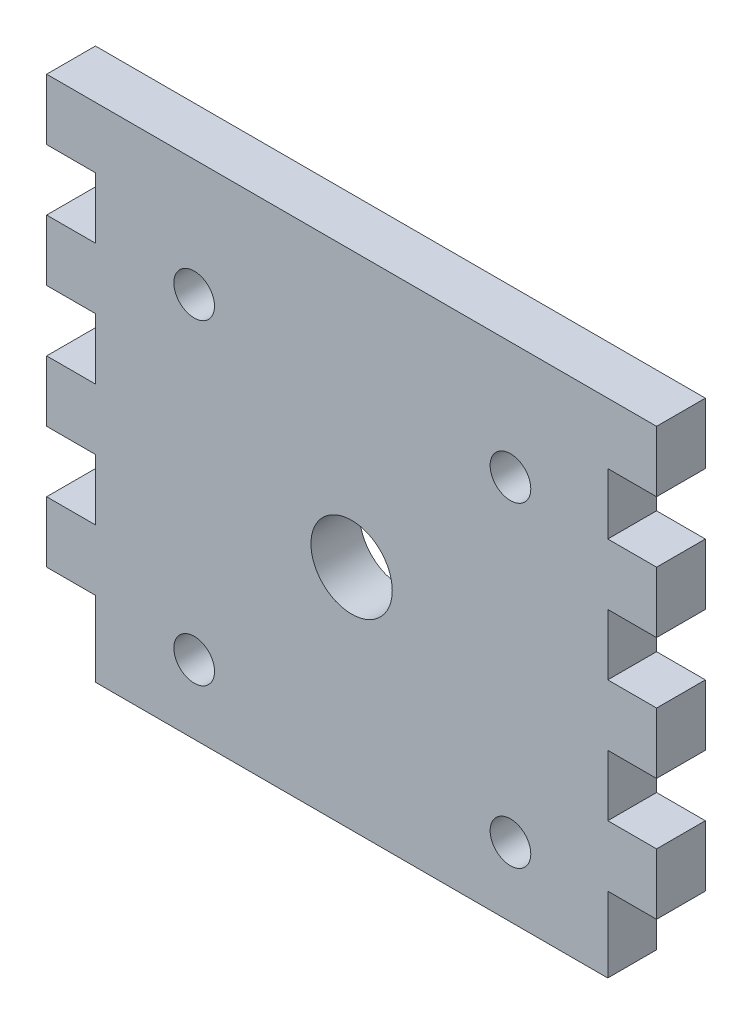
SolidWorks part; units mm, degrees
material "Thornel VCB-20 Carbon Cloth"
ref_plane "Front Plane" through (0, 0, 0) normal (0, 0, 1) x (1, 0, 0)
ref_plane "Top Plane" through (0, 0, 0) normal (0, 1, 0) x (1, 0, 0)
ref_plane "Right Plane" through (0, 0, 0) normal (1, 0, 0) x (0, 0, -1)
sketch "Sketch1" plane through (0, 0, 0) normal (0, 0, 1) x (1, 0, 0)
  line L1 (-37.8801, 17.0433) -> (38.3199, 17.0433)
  line L2 (-37.8801, 17.0433) -> (-37.8801, -59.1567)
  line L3 (-37.8801, -59.1567) -> (38.3199, -59.1567)
  line L4 (38.3199, 17.0433) -> (38.3199, -59.1567)
  dimension "D1" = 76.2
  dimension "D2" = 76.2
extrude "Boss-Extrude1" add sketch "Sketch1" along normal blind 6.35
sketch "Sketch2" plane through (0, 0, 6.35) normal (0, 0, 1) x (1, 0, 0)
  line L0 (-37.8801, 17.0433) -> (-31.5301, 17.0433)
  line L1 (38.3199, 17.0433) -> (-37.8801, 17.0433) construction
  line L2 (-31.5301, 17.0433) -> (-31.5301, 9.4233)
  line L3 (-31.5301, 9.4233) -> (-37.8801, 9.4233)
  line L4 (-37.8801, 17.0433) -> (-37.8801, -59.1567) construction
  line L5 (-37.8801, 9.4233) -> (-37.8801, 1.8033)
  line L6 (-37.8801, 1.8033) -> (-31.5301, 1.8033)
  line L7 (-31.5301, 1.8033) -> (-31.5301, -5.8167)
  line L8 (-31.5301, -5.8167) -> (-37.8801, -5.8167)
  line L9 (-37.8801, -5.8167) -> (-37.8801, -13.4367)
  line L10 (-37.8801, -13.4367) -> (-31.5301, -13.4367)
  line L11 (-31.5301, -13.4367) -> (-31.5301, -21.0567)
  line L12 (-31.5301, -21.0567) -> (-37.8801, -21.0567)
  line L13 (-37.8801, -21.0567) -> (-46.7258, -21.0567)
  line L14 (-37.8801, -21.0567) -> (-37.8801, -28.6767) [skipped]
  line L15 (-46.7258, -21.0567) -> (-46.7258, 17.0433)
  line L16 (-46.7258, 17.0433) -> (-37.8801, 17.0433)
  line L19 (47.1657, -21.0567) -> (47.1657, 17.0433)
  line L20 (38.3199, -21.0567) -> (47.1657, -21.0567)
  line L21 (31.9699, -21.0567) -> (38.3199, -21.0567)
  line L22 (31.9699, -13.4367) -> (31.9699, -21.0567)
  line L23 (38.3199, -13.4367) -> (31.9699, -13.4367)
  line L24 (38.3199, -5.8167) -> (38.3199, -13.4367)
  line L25 (31.9699, -5.8167) -> (38.3199, -5.8167)
  line L26 (31.9699, 1.8033) -> (31.9699, -5.8167)
  line L27 (38.3199, 1.8033) -> (31.9699, 1.8033)
  line L28 (38.3199, 9.4233) -> (38.3199, 1.8033)
  line L29 (31.9699, 9.4233) -> (38.3199, 9.4233)
  line L30 (31.9699, 17.0433) -> (31.9699, 9.4233)
  line L31 (38.3199, 17.0433) -> (31.9699, 17.0433)
  line L32 (47.1657, 17.0433) -> (38.3199, 17.0433)
  dimension "D1" = 7.62
  dimension "D2" = 7.62
  dimension "D3" = 6.35
  dimension "D4" = 6.35
  dimension "D6" = 38.1
  dimension "D5" = 3
extrude "Cut-Extrude1" cut sketch "Sketch2" against normal blind 6.35
sketch "Sketch3" plane through (0, 0, 6.35) normal (0, 0, 1) x (1, 0, 0)
  line L1 (-31.5301, -21.0567) -> (-37.8801, -21.0567)
  line L2 (-31.5301, -21.0567) -> (-31.5301, -59.1567)
  line L3 (-31.5301, -59.1567) -> (-37.8801, -59.1567)
  line L4 (-37.8801, -21.0567) -> (-37.8801, -59.1567)
  line L5 (31.9699, -21.0567) -> (38.3199, -21.0567)
  line L6 (31.9699, -21.0567) -> (31.9699, -59.1567)
  line L7 (31.9699, -59.1567) -> (38.3199, -59.1567)
  line L8 (38.3199, -21.0567) -> (38.3199, -59.1567)
extrude "Cut-Extrude2" cut sketch "Sketch3" against normal blind 6.35
sketch "Sketch4" plane through (0, 0, 6.35) normal (0, 0, 1) x (1, 0, 0)
  line L0 (-31.5301, -13.4367) -> (-31.5301, -21.0567)
  line L1 (-31.5301, -59.1567) -> (-31.5301, -13.4367) construction
  line L2 (-31.5301, -21.0567) -> (-37.6261, -21.0567)
  line L3 (-37.6261, -21.0567) -> (-37.6261, -28.6767)
  line L4 (-37.6261, -28.6767) -> (-31.5301, -28.6767)
  line L5 (-31.5301, -21.0567) -> (-31.5301, -28.6767)
  line L6 (0.2199, 17.0433) -> (0.2199, -59.1567)
  line L7 (31.9699, 17.0433) -> (-31.5301, 17.0433) construction
  line L8 (-31.5301, -59.1567) -> (31.9699, -59.1567) construction
  line L9 (31.9699, -21.0567) -> (38.0659, -21.0567)
  line L10 (38.0659, -21.0567) -> (38.0659, -28.6767)
  line L11 (38.0659, -28.6767) -> (31.9699, -28.6767)
  line L12 (31.9699, -21.0567) -> (31.9699, -28.6767)
  line M6 (-31.5301, -13.4367) -> (-31.5301, -59.1567)
  line M8 (31.9699, -59.1567) -> (31.9699, -13.4367)
  dimension "D1" = 7.62
  dimension "D2" = 7.62
  dimension "D3" = 6.096
  dimension "D4" = 6.096
extrude "Boss-Extrude3" add sketch "Sketch4" against normal blind 6.096 contours L3 L4 L2 M6 | L11 L10 L9 M8 region at (-34.5781, -24.8667, 6.35) region at (35.0179, -24.8667, 6.35)
sketch "Sketch5" plane through (0, 17.0433, 0) normal (0, 1, 0) x (1, 0, 0)
  line L1 (-31.5301, 0) -> (31.9699, 0)
  line L2 (-31.5301, 0) -> (-31.5301, -6.35)
  line L3 (-31.5301, -6.35) -> (31.9699, -6.35)
  line L4 (31.9699, 0) -> (31.9699, -6.35)
extrude "Cut-Extrude3" cut sketch "Sketch5" against normal blind 7.62
sketch "Sketch6" plane through (0, 0, 6.35) normal (0, 0, 1) x (1, 0, 0)
  line L0 (-31.5301, -59.1567) -> (31.9699, -59.1567) construction
  line L1 (-19.4468, -5.1999) -> (0.2199, -24.8667) construction
  line L2 (0.2199, -24.8667) -> (-37.8801, -24.8667) construction
  circle A0 centre (0.2199, -24.8667) radius 5.08
  circle A5 centre (-19.4468, -5.1999) radius 2.54
  circle A6 centre (20.0663, -5.1999) radius 2.54
  circle A7 centre (20.0663, -44.7131) radius 2.54
  circle A8 centre (-19.4468, -44.7131) radius 2.54
  point P16 (0.2825, -24.9292)
  point P18 (0.3097, -24.9565)
  dimension "D3" = 10.16
  dimension "D6" = 4
  dimension "D8" = 5.08
  dimension "D1" = 34.29
  dimension "D2" = 31.75
  dimension "D4" = 45
  dimension "D5" = 27.813
extrude "Cut-Extrude4" cut sketch "Sketch6" against normal through all
sketch "Sketch7" plane through (0, 0, 6.35) normal (0, 0, 1) x (1, 0, 0)
  line L0 (-31.5301, -28.6767) -> (-31.5301, -36.2967)
  line L1 (-31.5301, -59.1567) -> (-31.5301, -28.6767) construction
  line L2 (-31.5301, -36.2967) -> (-37.8801, -36.2967)
  line L3 (31.9699, -28.6767) -> (31.9699, -36.2967)
  line L4 (31.9699, -28.6767) -> (31.9699, -59.1567) construction
  line L5 (31.9699, -36.2967) -> (38.3199, -36.2967)
  line L6 (-37.8801, -36.2967) -> (-37.8801, -43.9167)
  line L7 (-37.8801, -43.9167) -> (-31.5301, -43.9167)
  line L8 (38.3199, -36.2967) -> (38.3199, -43.9167)
  line L9 (38.3199, -43.9167) -> (31.9699, -43.9167)
  line L12 (-31.5301, -43.9167) -> (-31.5301, -59.1567)
  line M27 (-31.5301, -28.6767) -> (-31.5301, -59.1567)
  line M29 (31.9699, -59.1567) -> (31.9699, -28.6767)
  dimension "D1" = 7.62
  dimension "D2" = 6.35
  dimension "D3" = 7.62
  dimension "D4" = 6.35
  dimension "D5" = 7.62
  dimension "D6" = 7.62
  dimension "D7" = 6.35
  dimension "D8" = 6.35
extrude "Boss-Extrude4" add sketch "Sketch7" against normal blind 6.35 contours L6 L7 L2 M27 | L9 L8 L5 M29 region at (-34.7051, -40.1067, 6.35) region at (35.1449, -40.1067, 6.35)
sketch "Sketch8" plane through (0, 0, 6.35) normal (0, 0, 1) x (1, 0, 0)
sketch "Sketch9" plane through (0, 0, 6.35) normal (0, 0, 1) x (1, 0, 0)
  line L0 (-31.5301, -43.9167) -> (-31.5301, -59.1567)
  line L1 (-31.5301, -59.1567) -> (31.9699, -59.1567)
  line L2 (31.9699, -59.1567) -> (31.9699, -43.9167)
  line L3 (31.9699, -43.9167) -> (31.9699, -59.1567) construction
  line L6 (-31.5301, -53.3208) -> (31.9699, -53.3208)
  line L7 (-31.5301, -53.3208) -> (-31.5301, -59.1567)
  line L8 (-31.5301, -59.1567) -> (31.9699, -59.1567)
  line L9 (31.9699, -53.3208) -> (31.9699, -59.1567)
  line M28 (-31.5301, -59.1567) -> (31.9699, -59.1567)
  line M29 (31.9699, -59.1567) -> (31.9699, -43.9167)
extrude "Cut-Extrude5" cut sketch "Sketch9" against normal blind 6.35 contours L6 L0 M28 M29 region at (0.2199, -56.2388, 6.35)
sketch "Sketch10" plane through (0, 1.8033, 0) normal (0, -1, 0) x (1, 0, 0)
  line L0 (38.3199, 0) -> (38.3199, 6.35) construction
  line L1 (31.9699, 0) -> (38.3199, 0)
  line L2 (31.9699, 0) -> (31.9699, 6.35)
  line L3 (31.9699, 6.35) -> (38.3199, 6.35)
  line L4 (38.3199, 0) -> (38.3199, 6.35)
  line L5 (38.3199, 6.35) -> (31.9699, 6.35) construction
extrude "Boss-Extrude5" add sketch "Sketch10" along normal blind 55.118
sketch "Sketch11" plane through (0, 1.8033, 0) normal (0, -1, 0) x (1, 0, 0)
  line L1 (-31.5301, 0) -> (-37.8801, 0)
  line L2 (-31.5301, 0) -> (-31.5301, 6.35)
  line L3 (-31.5301, 6.35) -> (-37.8801, 6.35)
  line L4 (-37.8801, 0) -> (-37.8801, 6.35)
extrude "Boss-Extrude6" add sketch "Sketch11" along normal blind 55.118
sketch "Sketch12" plane through (0, 0, 6.35) normal (0, 0, 1) x (1, 0, 0)
  line L0 (-37.8801, 9.4233) -> (-37.8801, 1.8033)
  line L1 (-37.8801, 9.4233) -> (-37.8801, -53.3147) construction
  line L2 (-37.8801, 1.8033) -> (-31.7841, 1.8033)
  line L3 (-31.7841, 1.8033) -> (-31.7841, -5.8167)
  line L4 (-31.7841, -5.8167) -> (-37.8801, -5.8167)
  line L5 (-37.8801, -5.8167) -> (-37.8801, -13.4367)
  line L6 (-37.8801, -13.4367) -> (-31.7841, -13.4367)
  line L7 (-31.7841, -13.4367) -> (-31.7841, -21.0567)
  line L8 (-31.7841, -21.0567) -> (-37.8801, -21.0567)
  line L9 (-37.8801, -21.0567) -> (-37.8801, -28.6767)
  line L10 (-37.8801, -28.6767) -> (-31.7841, -28.6767)
  line L11 (-31.7841, -28.6767) -> (-31.7841, -36.2967)
  line L12 (-31.7841, -36.2967) -> (-37.8801, -36.2967)
  line L13 (-37.8801, -36.2967) -> (-37.8801, -43.9167)
  line L14 (-37.8801, -43.9167) -> (-31.7841, -43.9167)
  line L15 (-31.7841, -43.9167) -> (-31.7841, -51.5367)
  line L16 (-31.7841, -51.5367) -> (-37.8801, -51.5367)
  line L17 (-37.8801, 9.4233) -> (-56.0123, 9.4233)
  line L18 (-56.0123, 9.4233) -> (-56.0123, -53.8176)
  line L19 (-56.0123, -53.8176) -> (-37.8801, -51.5367)
  line L20 (0.2199, 9.4233) -> (0.2199, -53.3208)
  line L21 (-37.8801, 9.4233) -> (38.3199, 9.4233) construction
  line L22 (-31.5301, -53.3208) -> (31.9699, -53.3208) construction
  line L23 (56.4521, 9.4233) -> (56.4521, -53.8176)
  line L24 (38.3199, 9.4233) -> (56.4521, 9.4233)
  line L25 (38.3199, 9.4233) -> (38.3199, 1.8033)
  line L26 (38.3199, 1.8033) -> (32.2239, 1.8033)
  line L27 (32.2239, 1.8033) -> (32.2239, -5.8167)
  line L28 (32.2239, -5.8167) -> (38.3199, -5.8167)
  line L29 (38.3199, -5.8167) -> (38.3199, -13.4367)
  line L30 (38.3199, -13.4367) -> (32.2239, -13.4367)
  line L31 (32.2239, -13.4367) -> (32.2239, -21.0567)
  line L32 (32.2239, -21.0567) -> (38.3199, -21.0567)
  line L33 (38.3199, -21.0567) -> (38.3199, -28.6767)
  line L34 (38.3199, -28.6767) -> (32.2239, -28.6767)
  line L35 (32.2239, -28.6767) -> (32.2239, -36.2967)
  line L36 (32.2239, -36.2967) -> (38.3199, -36.2967)
  line L37 (38.3199, -36.2967) -> (38.3199, -43.9167)
  line L38 (38.3199, -43.9167) -> (32.2239, -43.9167)
  line L39 (32.2239, -43.9167) -> (32.2239, -51.5367)
  line L40 (32.2239, -51.5367) -> (38.3199, -51.5367)
  line L41 (56.4521, -53.8176) -> (38.3199, -51.5367)
  line M26 (38.3199, -53.3147) -> (38.3199, 9.4233)
  line M28 (-37.8801, 9.4233) -> (-37.8801, -53.3147)
  dimension "D1" = 7.62
  dimension "D2" = 7.62
  dimension "D3" = 6.096
  dimension "D4" = 4
extrude "Cut-Extrude7" cut sketch "Sketch12" against normal blind 55.118 contours L18 L19 L17 M28 | L41 L23 L24 M26 | L39 L40 L38 M26 | L35 L36 L34 M26 | L31 L32 L30 M26 | L27 L28 L26 M26 | L4 L3 L2 M28 | L8 L7 L6 M28 | L12 L11 L10 M28 | L16 L15 L14 M28 region at (-47.0017, -21.6304, 6.35) region at (-34.8321, -2.0067, 6.35) region at (-34.8321, -17.2467, 6.35) region at (-34.8321, -47.7267, 6.35) region at (-34.8321, -32.4867, 6.35) region at (47.4415, -21.6304, 6.35) region at (35.2719, -47.7267, 6.35) region at (35.2719, -2.0067, 6.35) region at (35.2719, -32.4867, 6.35) region at (35.2719, -17.2467, 6.35)
sketch "Sketch16" plane through (0, -51.5367, 0) normal (0, 1, 0) x (1, 0, 0)
  line L1 (-37.8801, 0) -> (-31.7841, 0)
  line L2 (-37.8801, 0) -> (-37.8801, -6.35)
  line L3 (-37.8801, -6.35) -> (-31.7841, -6.35)
  line L4 (-31.7841, 0) -> (-31.7841, -6.35)
  line L5 (38.3199, 0) -> (32.2239, 0)
  line L6 (38.3199, 0) -> (38.3199, -6.35)
  line L7 (38.3199, -6.35) -> (32.2239, -6.35)
  line L8 (32.2239, 0) -> (32.2239, -6.35)
extrude "Cut-Extrude8" cut sketch "Sketch16" against normal blind 2.54
sketch "Sketch17" plane through (0, 9.4233, 0) normal (0, 1, 0) x (1, 0, 0)
  line L0 (38.3199, 0) -> (38.3199, -6.35) construction
  line L1 (-37.8801, 0) -> (38.3199, 0)
  line L2 (-37.8801, 0) -> (-37.8801, -0.254)
  line L3 (-37.8801, -0.254) -> (38.3199, -0.254)
  line L4 (38.3199, 0) -> (38.3199, -0.254)
  dimension "D1" = 0.254
extrude "Cut-Extrude9" cut sketch "Sketch17" against normal blind 72.898
